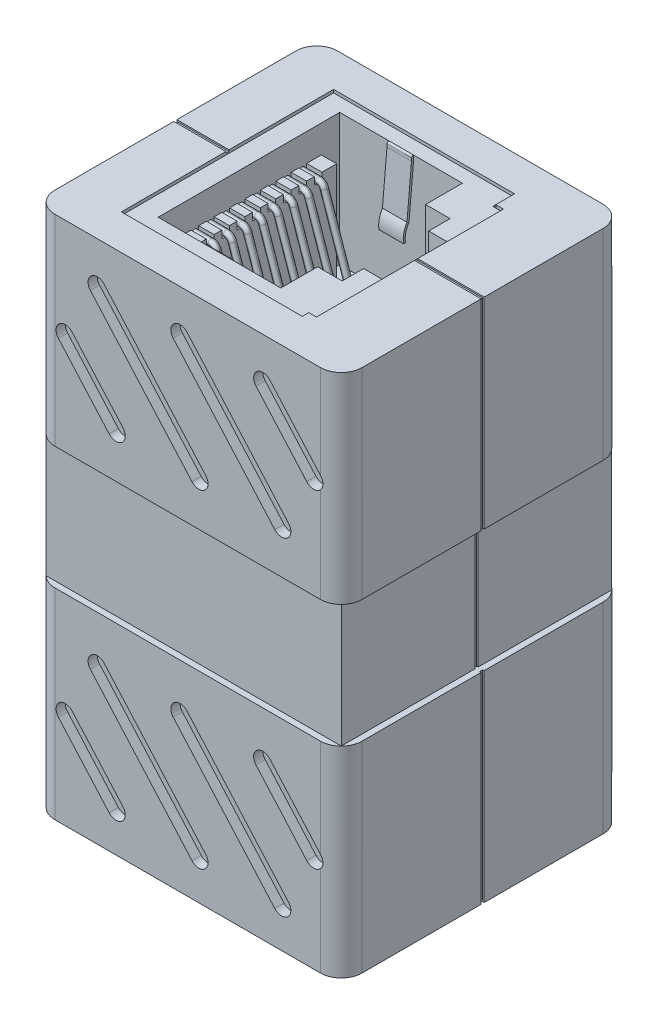
SolidWorks part; units mm, degrees
ref_plane "Front Plane" through (0, 0, 0) normal (0, 0, 1) x (1, 0, 0)
ref_plane "Top Plane" through (0, 0, 0) normal (0, 1, 0) x (1, 0, 0)
ref_plane "Right Plane" through (0, 0, 0) normal (1, 0, 0) x (0, 0, -1)
sketch "Sketch1" plane through (0, 0, 0) normal (0, 1, 0) x (1, 0, 0)
  line L0 (-9.3987, 11.8197) -> (9.9053, 11.8197)
  line L1 (-12.4726, 8.7458) -> (-12.4726, -8.5262)
  line L2 (-9.3987, -11.6) -> (9.9053, -11.6)
  line L3 (12.9792, 8.7458) -> (12.9792, -8.5262)
  line L4 (-12.4726, -8.5262) -> (-12.4726, -11.6)
  line L5 (-12.4726, 8.7458) -> (-12.4726, 11.8197)
  line L6 (-12.4726, -11.6) -> (-9.3987, -11.6)
  line L7 (9.9053, 11.8197) -> (12.9792, 11.8197)
  line L8 (-12.4726, 11.8197) -> (-9.3987, 11.8197)
  line L9 (12.9792, -8.5262) -> (12.9792, -11.6)
  line L10 (12.9792, 11.8197) -> (12.9792, 8.7458)
  line L11 (12.9792, -11.6) -> (9.9053, -11.6)
  dimension "D1" = 19.304
  dimension "D2" = 17.272
extrude "Boss-Extrude1" add sketch "Sketch1" along normal blind 43.434
ref_plane "Plane1" through (0, 43.434, 0) normal (0, 1, 0) x (1, 0, 0)
sketch "Sketch5" plane through (0, 43.434, 0) normal (0, 1, 0) x (1, 0, 0)
  line L0 (12.9792, 11.8197) -> (-12.4726, 11.8197) construction
  line L1 (6.7044, 8.7717) -> (-8.0276, 8.7717)
  line L2 (6.7044, 8.7717) -> (6.7044, 7.2218)
  line L3 (6.7044, -8.552) -> (-8.0276, -8.552)
  line L4 (-8.0276, 8.7717) -> (-8.0276, -8.552)
  line L5 (-12.4726, -11.6) -> (12.9792, -11.6) construction
  line L6 (6.8314, 8.8987) -> (6.8314, 7.3488)
  line L7 (-12.4726, 11.8197) -> (-12.4726, -11.6) construction
  line L8 (-8.1546, 8.8987) -> (-8.1546, -8.679)
  line L9 (6.7044, -8.0182) -> (6.7044, -8.552)
  line L10 (6.7044, -8.0182) -> (7.3394, -8.0182)
  line L11 (-8.1546, -8.679) -> (6.8314, -8.679)
  line L12 (6.7044, 7.2218) -> (7.3394, 7.2218)
  line L13 (7.3394, -8.0182) -> (7.3394, 7.2218)
  line L14 (6.8314, -8.679) -> (6.8314, -8.1452)
  line L15 (6.8314, -8.1452) -> (7.4664, -8.1452)
  line L16 (7.4664, -8.1452) -> (7.4664, 7.3488)
  line L17 (7.4664, 7.3488) -> (6.8314, 7.3488)
  line L19 (6.8314, 8.8987) -> (-8.1546, 8.8987)
  dimension "D1" = 3.048
  dimension "D2" = 3.048
  dimension "D3" = 4.445
  dimension "D4" = 14.732
  dimension "D5" = 0.127
  dimension "D6" = 0.127
  dimension "D7" = 0.127
  dimension "D8" = 0.127
  dimension "D9" = 0.127
  dimension "D10" = 0.127
  dimension "D11" = 0.127
  dimension "D12" = 0.127
extrude "Cut-Extrude4" cut sketch "Sketch5" against normal blind 0.254
sketch "Sketch6" plane through (0, 43.434, 0) normal (0, 1, 0) x (1, 0, 0)
  line L0 (-12.4726, 11.8197) -> (-12.4726, -11.6) construction
  line L1 (12.9792, 0.2368) -> (-12.4726, 0.2368)
  line L2 (12.9792, -0.0172) -> (12.9792, 0.2368)
  line L3 (12.9792, -0.0172) -> (-12.4726, -0.0172)
  line L4 (-12.4726, 0.2368) -> (-12.4726, -0.0172)
  line L5 (-12.4726, 0.1098) -> (-12.4726, -0.0172) construction
  line L6 (-12.4726, 0.1098) -> (-12.4726, 0.2368) construction
  point P0 (-12.4726, 0.1098)
  dimension "D1" = 0.254
  dimension "D2" = 0
extrude "Cut-Extrude7" cut sketch "Sketch6" against normal blind 0.127
sketch "Sketch7" plane through (12.9792, 0, 0) normal (1, 0, 0) x (0, 0, -1)
  line L0 (-0.0172, 43.307) -> (0.2368, 43.307)
  line L1 (0.2368, 43.307) -> (0.2368, 0)
  line L2 (-11.6, 0) -> (11.8197, 0) construction
  line L3 (0.2368, 0) -> (-0.0172, 0)
  line L4 (-0.0172, 0) -> (-0.0172, 43.307)
extrude "Cut-Extrude8" cut sketch "Sketch7" against normal blind 0.127
sketch "Sketch8" plane through (-12.4726, 0, 0) normal (-1, 0, 0) x (0, 0, 1)
  line L0 (-0.2368, 43.307) -> (0.0172, 43.307)
  line L1 (0.0172, 43.307) -> (0.0172, 0)
  line L2 (-0.2368, 0) -> (-0.2368, 43.307)
  line L3 (-0.2368, 0) -> (0.0172, 0)
  line L4 (-11.8197, 0) -> (11.6, 0) construction
extrude "Cut-Extrude9" cut sketch "Sketch8" against normal blind 0.127
sketch "Sketch9" plane through (0, 0, 0) normal (0, -1, 0) x (1, 0, 0)
  line L0 (-12.3456, 0.0172) -> (-12.3456, -0.2368)
  line L1 (-12.3456, -0.2368) -> (12.8522, -0.2368)
  line L2 (12.8522, -0.2368) -> (12.8522, 0.0172)
  line L3 (12.8522, 0.0172) -> (-12.3456, 0.0172)
extrude "Cut-Extrude10" cut sketch "Sketch9" against normal blind 0.127
sketch "Sketch10" plane through (0, 0, 11.6) normal (0, 0, 1) x (1, 0, 0)
  line L0 (0.2533, 43.434) -> (0.2533, 0) construction
  line L3 (-12.4726, 43.434) -> (12.9792, 43.434) construction
  line L4 (-17.0116, 16.637) -> (17.5183, 16.637)
  line L5 (-17.0116, 16.637) -> (-17.0116, 26.797)
  line L6 (-17.0116, 26.797) -> (17.5183, 26.797)
  line L7 (17.5183, 16.637) -> (17.5183, 26.797)
  line L8 (-17.0116, 16.637) -> (17.5183, 26.797) construction
  line L9 (-17.0116, 26.797) -> (17.5183, 16.637) construction
  line L10 (-12.4726, 0) -> (12.9792, 0) construction
  line L11 (0.2533, 21.717) -> (12.9792, 21.717) construction
  line L12 (12.9792, 43.434) -> (12.9792, 0) construction
  point P6 (0.2533, 21.717)
  dimension "D1" = 10.16
  dimension "D2" = 0
extrude "Cut-Extrude11" cut sketch "Sketch10" against normal blind 0.508
sketch "Sketch11" plane through (12.9792, 0, 0) normal (1, 0, 0) x (0, 0, -1)
  line L0 (-0.0172, 21.717) -> (-11.092, 21.717) construction
  line L1 (-0.0172, 0) -> (-0.0172, 43.434) construction
  line L2 (-11.092, 26.797) -> (-11.092, 16.637) construction
  line L4 (-13.4166, 16.637) -> (13.3823, 16.637)
  line L5 (-13.4166, 16.637) -> (-13.4166, 26.797)
  line L6 (-13.4166, 26.797) -> (13.3823, 26.797)
  line L7 (13.3823, 16.637) -> (13.3823, 26.797)
  line L8 (-13.4166, 16.637) -> (13.3823, 26.797) construction
  line L9 (-13.4166, 26.797) -> (13.3823, 16.637) construction
  dimension "D1" = 10.16
extrude "Cut-Extrude12" cut sketch "Sketch11" against normal blind 0.508
sketch "Sketch12" plane through (0, 0, -11.8197) normal (0, 0, -1) x (-1, 0, 0)
  line L0 (-0.2533, 0) -> (-0.2533, 43.7001) construction
  line L1 (-12.9792, 0) -> (12.4726, 0) construction
  line L3 (-14.7409, 16.7701) -> (14.2342, 16.7701)
  line L4 (-14.7409, 16.7701) -> (-14.7409, 26.9301)
  line L5 (-14.7409, 26.9301) -> (14.2342, 26.9301)
  line L6 (14.2342, 16.7701) -> (14.2342, 26.9301)
  line L7 (-14.7409, 16.7701) -> (14.2342, 26.9301) construction
  line L8 (-14.7409, 26.9301) -> (14.2342, 16.7701) construction
  point P4 (-0.2533, 21.8501)
  dimension "D1" = 10.16
extrude "Cut-Extrude13" cut sketch "Sketch12" against normal blind 0.508
sketch "Sketch13" plane through (-12.4726, 0, 0) normal (-1, 0, 0) x (0, 0, 1)
  line L0 (0.0172, 21.717) -> (9.2132, 21.717) construction
  line L1 (0.0172, 0) -> (0.0172, 43.434) construction
  line L3 (-17.8132, 16.637) -> (17.8475, 16.637)
  line L4 (-17.8132, 16.637) -> (-17.8132, 26.797)
  line L5 (-17.8132, 26.797) -> (17.8475, 26.797)
  line L6 (17.8475, 16.637) -> (17.8475, 26.797)
  line L7 (-17.8132, 16.637) -> (17.8475, 26.797) construction
  line L8 (-17.8132, 26.797) -> (17.8475, 16.637) construction
  dimension "D1" = 10.16
extrude "Cut-Extrude14" cut sketch "Sketch13" against normal blind 0.508
sketch "Sketch14" plane through (-11.9646, 0, 0) normal (-1, 0, 0) x (0, 0, 1)
  line L0 (-0.2368, 26.797) -> (0.0172, 26.797)
  line L1 (0.0172, 26.797) -> (0.0172, 16.637)
  line L2 (0.0172, 16.637) -> (-0.2368, 16.637)
  line L3 (-0.2368, 16.637) -> (-0.2368, 26.797)
extrude "Cut-Extrude15" cut sketch "Sketch14" against normal blind 0.127
sketch "Sketch15" plane through (12.4712, 0, 0) normal (1, 0, 0) x (0, 0, -1)
  line L0 (-0.0172, 26.797) -> (0.2368, 26.797)
  line L1 (0.2368, 26.797) -> (0.2368, 16.637)
  line L2 (0.2368, 16.637) -> (-0.0172, 16.637)
  line L3 (-0.0172, 16.637) -> (-0.0172, 26.797)
extrude "Cut-Extrude16" cut sketch "Sketch15" against normal blind 0.127
sketch "Sketch16" plane through (0, 0, -11.8197) normal (0, 0, -1) x (-1, 0, 0)
  line L0 (-6.486, 39.9428) -> (12.1668, 39.9428) construction
  line L1 (7.23, 39.9428) -> (-1.1844, 30.4303) construction
  line L2 (5.6736, 30.4303) -> (-11.4552, 30.4303) construction
  line L3 (7.23, 12.7648) -> (-1.1844, 3.2523) construction
  line L4 (7.8008, 12.2599) -> (-0.6137, 2.7474)
  line L5 (7.8008, 39.4379) -> (-0.6137, 29.9254)
  line L6 (6.6593, 40.4476) -> (-1.7552, 30.9351)
  line L7 (0.372, 39.9428) -> (-8.0424, 30.4303) construction
  line L8 (0.9428, 39.4379) -> (-7.4717, 29.9254)
  line L9 (-0.1987, 40.4476) -> (-8.6132, 30.9351)
  line L10 (9.8808, 35.1865) -> (5.6736, 30.4303) construction
  line L11 (10.4515, 34.6816) -> (6.2443, 29.9254)
  line L12 (9.31, 35.6914) -> (5.1028, 30.9351)
  line L13 (-6.486, 39.9428) -> (-10.6932, 35.1865) construction
  line L14 (-5.9152, 39.4379) -> (-10.1225, 34.6816)
  line L15 (-7.0567, 40.4476) -> (-11.264, 35.6914)
  line L16 (-12.9792, 43.434) -> (-12.9792, 26.9301) construction
  line L17 (6.6593, 13.2696) -> (-1.7552, 3.7571)
  line L18 (0.372, 12.7648) -> (-8.0424, 3.2523) construction
  line L19 (0.9428, 12.2599) -> (-7.4717, 2.7474)
  line L20 (-0.1987, 13.2696) -> (-8.6132, 3.7571)
  line L21 (9.8808, 8.0085) -> (5.6736, 3.2523) construction
  line L22 (10.4515, 7.5036) -> (6.2443, 2.7474)
  line L23 (9.31, 8.5134) -> (5.1028, 3.7571)
  line L24 (-6.486, 12.7648) -> (-10.6932, 8.0085) construction
  line L25 (-5.9152, 12.2599) -> (-10.1225, 7.5036)
  line L26 (-7.0567, 13.2696) -> (-11.264, 8.5134)
  arc A0 (7.8008, 39.4379) -> (6.6593, 40.4476) centre (7.23, 39.9428) ccw
  arc A1 (-1.7552, 30.9351) -> (-0.6137, 29.9254) centre (-1.1844, 30.4303) ccw
  arc A2 (0.9428, 39.4379) -> (-0.1987, 40.4476) centre (0.372, 39.9428) ccw
  arc A3 (-8.6132, 30.9351) -> (-7.4717, 29.9254) centre (-8.0424, 30.4303) ccw
  arc A4 (10.4515, 34.6816) -> (9.31, 35.6914) centre (9.8808, 35.1865) ccw
  arc A5 (5.1028, 30.9351) -> (6.2443, 29.9254) centre (5.6736, 30.4303) ccw
  arc A6 (-5.9152, 39.4379) -> (-7.0567, 40.4476) centre (-6.486, 39.9428) ccw
  arc A7 (-11.264, 35.6914) -> (-10.1225, 34.6816) centre (-10.6932, 35.1865) ccw
  arc A8 (7.8008, 12.2599) -> (6.6593, 13.2696) centre (7.23, 12.7648) ccw
  arc A9 (-1.7552, 3.7571) -> (-0.6137, 2.7474) centre (-1.1844, 3.2523) ccw
  arc A10 (0.9428, 12.2599) -> (-0.1987, 13.2696) centre (0.372, 12.7648) ccw
  arc A11 (-8.6132, 3.7571) -> (-7.4717, 2.7474) centre (-8.0424, 3.2523) ccw
  arc A12 (10.4515, 7.5036) -> (9.31, 8.5134) centre (9.8808, 8.0085) ccw
  arc A13 (5.1028, 3.7571) -> (6.2443, 2.7474) centre (5.6736, 3.2523) ccw
  arc A14 (-5.9152, 12.2599) -> (-7.0567, 13.2696) centre (-6.486, 12.7648) ccw
  arc A15 (-11.264, 8.5134) -> (-10.1225, 7.5036) centre (-10.6932, 8.0085) ccw
  point P10 (3.0228, 35.1865)
  point P15 (-3.8352, 35.1865)
  point P22 (7.7772, 32.8084)
  point P29 (-8.5896, 37.5646)
  point P36 (-12.9792, 35.182)
  point P39 (3.0228, 8.0085)
  point P44 (-3.8352, 8.0085)
  point P51 (7.7772, 5.6304)
  point P58 (-8.5896, 10.3866)
  dimension "D2" = 12.7
  dimension "D3" = 6.35
  dimension "D4" = 6.35
  dimension "D5" = 1.524
  dimension "D6" = 1.524
  dimension "D7" = 1.524
  dimension "D8" = 1.524
  dimension "D9" = 6.858
  dimension "D10" = 6.858
  dimension "D11" = 6.858
  dimension "D12" = 2.286
  dimension "D13" = 12.7
extrude "Cut-Extrude17" cut sketch "Sketch16" against normal blind 0.762
ref_plane "Plane4" through (0, 0, -0.1098) normal (0, 0, -1) x (-1, 0, 0)
mirror "Mirror1" about plane through (0, 0, -0.1098) normal (0, 0, -1) of "Cut-Extrude17"
sketch "Sketch17" plane through (0, 43.434, 0) normal (0, 1, 0) x (1, 0, 0)
  line L0 (6.7044, -8.0182) -> (6.7044, -8.552)
  line L1 (-8.0276, 8.7717) -> (6.7044, 8.7717)
  line L2 (-8.0276, 8.7717) -> (-8.0276, -8.552)
  line L3 (-8.0276, -8.552) -> (6.7044, -8.552)
  line L4 (6.7044, 8.7717) -> (6.7044, 7.2218)
  line L5 (7.3394, -8.0182) -> (6.7044, -8.0182)
  line L6 (7.3394, -8.0182) -> (7.3394, 7.2218)
  line L7 (7.3394, 7.2218) -> (6.7044, 7.2218)
extrude "Cut-Extrude18" cut sketch "Sketch17" against normal blind 0.127
sketch "Sketch18" plane through (0, 43.307, 0) normal (0, 1, 0) x (1, 0, 0)
  line L0 (3.7834, -4.3621) -> (3.7834, -7.4101)
  line L1 (-6.3766, 7.6297) -> (3.7834, 7.6297)
  line L2 (-6.3766, 7.6297) -> (-6.3766, -7.4101)
  line L3 (-6.3766, -7.4101) -> (3.7834, -7.4101)
  line L4 (3.7834, 7.6297) -> (3.7834, 4.5817)
  line L5 (3.7834, 4.5817) -> (5.8154, 4.5817)
  line L6 (5.8154, -2.5841) -> (5.8154, -4.3621)
  line L7 (3.7834, -4.3621) -> (5.8154, -4.3621)
  line L8 (5.8154, 4.5817) -> (5.8154, 2.8037)
  line L9 (5.8154, 2.8037) -> (7.3394, 2.8037)
  line L11 (5.8154, -2.5841) -> (7.3394, -2.5841)
  line L12 (7.4664, 0.2368) -> (7.4664, 7.3488) construction
  line L13 (-6.3766, 0.1098) -> (-5.755, 0.1098) construction
  line L16 (-8.0276, 0.1098) -> (-7.4203, 0.1098) construction
  line L17 (-8.0276, 8.7717) -> (-8.0276, -8.552) construction
  line L18 (7.3394, 2.8037) -> (7.4664, 2.8037)
  line L19 (7.4664, 2.8037) -> (7.4664, -2.5841)
  line L20 (7.4664, -2.5841) -> (7.3394, -2.5841)
  dimension "D1" = 3.048
  dimension "D2" = 3.048
  dimension "D3" = 1.778
  dimension "D4" = 1.778
  dimension "D5" = 2.032
  dimension "D6" = 1.524
  dimension "D7" = 0
  dimension "D8" = 10.16
extrude "Cut-Extrude19" cut sketch "Sketch18" against normal blind 0.762
sketch "Sketch20" plane through (0, 42.545, 0) normal (0, 1, 0) x (1, 0, 0)
  line L0 (-6.3766, -7.4101) -> (3.7834, -7.4101)
  line L1 (3.7834, -7.4101) -> (3.7834, -4.3621)
  line L2 (3.7834, -4.3621) -> (5.8154, -4.3621)
  line L3 (5.8154, -4.3621) -> (5.8154, -2.5841)
  line L4 (5.8154, -2.5841) -> (6.5774, -2.5841)
  line L6 (6.5774, -2.5841) -> (6.5774, 2.8037)
  line L7 (7.3394, 2.8037) -> (5.8154, 2.8037) construction
  line L8 (6.5774, 2.8037) -> (5.8154, 2.8037)
  line L9 (5.8154, 2.8037) -> (5.8154, 4.5817)
  line L10 (5.8154, 4.5817) -> (3.7834, 4.5817)
  line L11 (3.7834, 4.5817) -> (3.7834, 7.6297)
  line L12 (3.7834, 7.6297) -> (-6.3766, 7.6297)
  line L13 (-6.3766, 7.6297) -> (-6.3766, -7.4101)
extrude "Cut-Extrude20" cut sketch "Sketch20" against normal blind 10.16
fillet "Fillet1" radius 1.7272 16 edges at (12.9792, 8.3185, 11.6) (-12.4726, 8.3185, 11.6) (-12.4726, 35.1155, 11.6) (-12.4726, 35.182, -11.8197) (12.9792, 35.182, -11.8197) (12.9792, 35.1155, 11.6) (12.9792, 8.3185, -11.8197) (12.7252, 16.637, -11.8197) (12.4712, 16.7035, -11.8197) (-12.4726, 26.9301, -11.5657) (12.9792, 26.9301, -11.5657) (-12.4726, 26.8635, -11.3117) (12.9792, 26.8635, -11.3117) (-12.4726, 8.3185, -11.8197) (-12.2186, 16.637, -11.8197) (-11.9646, 16.7035, -11.8197)
ref_plane "Plane5" through (-1.2966, 0, 0) normal (-1, 0, 0) x (0, 0, 1)
sketch "Sketch21" plane through (-1.2966, 0, 0) normal (-1, 0, 0) x (0, 0, 1)
  line L0 (-7.4785, 42.9304) -> (-7.1025, 38.7375)
  line L1 (-8.8987, 43.18) -> (8.679, 43.18) construction
  line L2 (-7.6297, 32.385) -> (-7.6297, 43.307) construction
  line L3 (-7.2722, 38.6632) -> (-7.6297, 42.6506)
  line L4 (-6.8187, 37.3348) -> (-6.9856, 37.3348)
  line L6 (-0.1098, 32.385) -> (-0.1098, 44.847) construction
  line L7 (-7.6297, 32.385) -> (7.4101, 32.385) construction
  line L8 (-7.6297, 43.18) -> (-7.6297, 42.6506)
  line L10 (7.4101, 43.307) -> (7.4101, 43.18)
  line L11 (7.2734, 43.1621) -> (7.2589, 42.9304)
  line L12 (7.4101, 43.18) -> (7.4101, 42.6506)
  line L13 (-7.4931, 43.1621) -> (-7.4785, 42.9304)
  line L15 (-7.6297, 43.307) -> (-7.6297, 43.18)
  line L17 (6.599, 37.3348) -> (6.766, 37.3348)
  line L18 (7.0525, 38.6632) -> (7.4101, 42.6506)
  line L19 (7.2589, 42.9304) -> (6.8829, 38.7375)
  spline S0 degree 2 poles (-7.1025, 38.7375) (-6.7036, 38.0831) (-6.8187, 37.3348) knots 0 0 0 1 1 1
  spline S1 degree 2 poles (-6.9856, 37.3348) (-6.8588, 38.0538) (-7.2722, 38.6632) knots 0 0 0 1 1 1
  spline S2 degree 2 poles (7.4101, 43.307) (7.2928, 43.2827) (7.2734, 43.1621) knots 0 0 0 1 1 1
  spline S3 degree 2 poles (6.766, 37.3348) (6.6391, 38.0538) (7.0525, 38.6632) knots 0 0 0 1 1 1
  spline S4 degree 2 poles (6.8829, 38.7375) (6.4839, 38.0831) (6.599, 37.3348) knots 0 0 0 1 1 1
  spline S6 degree 2 poles (-7.6297, 43.307) (-7.5125, 43.2827) (-7.4931, 43.1621) knots 0 0 0 1 1 1
extrude "Boss-Extrude2" add sketch "Sketch21" along normal blind 1.016 and the other way blind 1.016
sketch "Sketch22" plane through (-6.3766, 0, 0) normal (1, 0, 0) x (0, 0, -1)
  line L0 (6.1057, 32.385) -> (-5.8861, 32.385)
  line L1 (7.6297, 32.385) -> (-7.4101, 32.385) construction
  line L2 (-5.8861, 32.385) -> (-5.8861, 41.021)
  line L3 (-5.8861, 41.021) -> (6.1057, 41.021)
  line L4 (6.1057, 41.021) -> (6.1057, 32.385)
  line L5 (7.6297, 43.307) -> (-7.4101, 43.307) construction
  line L6 (-7.4101, 32.385) -> (-7.4101, 43.307) construction
  line L7 (7.6297, 32.385) -> (7.6297, 43.307) construction
  dimension "D1" = 2.286
  dimension "D2" = 1.524
  dimension "D3" = 1.524
extrude "Boss-Extrude3" add sketch "Sketch22" along normal blind 1.27
sketch "Sketch23" plane through (-5.1066, 0, 0) normal (1, 0, 0) x (0, 0, -1)
  line L0 (6.1057, 41.021) -> (-5.8861, 41.021) construction
  line L1 (6.1057, 32.385) -> (6.1057, 41.021) construction
  line L2 (4.8865, 41.021) -> (4.2515, 41.021)
  line L3 (4.8865, 41.021) -> (4.8865, 40.386)
  line L4 (4.8865, 40.386) -> (4.2515, 40.386)
  line L5 (4.2515, 41.021) -> (4.2515, 40.386)
  line L6 (3.6093, 41.021) -> (2.9743, 41.021)
  line L7 (3.6093, 41.021) -> (3.6093, 40.386)
  line L8 (3.6093, 40.386) -> (2.9743, 40.386)
  line L9 (2.9743, 41.021) -> (2.9743, 40.386)
  line L10 (2.332, 41.021) -> (1.697, 41.021)
  line L11 (2.332, 41.021) -> (2.332, 40.386)
  line L12 (2.332, 40.386) -> (1.697, 40.386)
  line L13 (1.697, 41.021) -> (1.697, 40.386)
  line L14 (1.0548, 41.021) -> (0.4198, 41.021)
  line L15 (1.0548, 41.021) -> (1.0548, 40.386)
  line L16 (1.0548, 40.386) -> (0.4198, 40.386)
  line L17 (0.4198, 41.021) -> (0.4198, 40.386)
  line L18 (-0.2225, 41.021) -> (-0.8575, 41.021)
  line L19 (-0.2225, 41.021) -> (-0.2225, 40.386)
  line L20 (-0.2225, 40.386) -> (-0.8575, 40.386)
  line L21 (-0.8575, 41.021) -> (-0.8575, 40.386)
  line L22 (-1.4998, 41.021) -> (-2.1348, 41.021)
  line L23 (-1.4998, 41.021) -> (-1.4998, 40.386)
  line L24 (-1.4998, 40.386) -> (-2.1348, 40.386)
  line L25 (-2.1348, 41.021) -> (-2.1348, 40.386)
  line L26 (-2.777, 41.021) -> (-3.412, 41.021)
  line L27 (-2.777, 41.021) -> (-2.777, 40.386)
  line L28 (-2.777, 40.386) -> (-3.412, 40.386)
  line L29 (-3.412, 41.021) -> (-3.412, 40.386)
  line L30 (-4.0543, 41.021) -> (-4.6893, 41.021)
  line L31 (-4.0543, 41.021) -> (-4.0543, 40.386)
  line L32 (-4.0543, 40.386) -> (-4.6893, 40.386)
  line L33 (-4.6893, 41.021) -> (-4.6893, 40.386)
  dimension "D1" = 0.635
  dimension "D2" = 0.635
  dimension "D3" = 1.2192
  dimension "D4" = 8
extrude "Cut-Extrude24" cut sketch "Sketch23" against normal blind 1.27
sketch "Sketch25" plane through (0, 32.385, 0) normal (0, 1, 0) x (1, 0, 0)
  line L0 (-2.3163, 3.6165) -> (-2.3163, 2.9815)
  line L1 (-1.6813, 4.8865) -> (-2.3163, 4.8865)
  line L2 (-1.6813, 4.8865) -> (-1.6813, 4.2515)
  line L3 (-1.6813, 4.2515) -> (-2.3163, 4.2515)
  line L4 (-2.3163, 4.8865) -> (-2.3163, 4.2515)
  line L5 (-1.6813, 2.9815) -> (-2.3163, 2.9815)
  line L6 (-1.6813, 3.6165) -> (-1.6813, 2.9815)
  line L7 (-1.6813, 3.6165) -> (-2.3163, 3.6165)
  line L8 (-2.3163, 2.3465) -> (-2.3163, 1.7115)
  line L9 (-1.6813, 1.7115) -> (-2.3163, 1.7115)
  line L10 (-1.6813, 2.3465) -> (-1.6813, 1.7115)
  line L11 (-1.6813, 2.3465) -> (-2.3163, 2.3465)
  line L12 (-2.3163, 1.0765) -> (-2.3163, 0.4415)
  line L13 (-1.6813, 0.4415) -> (-2.3163, 0.4415)
  line L14 (-1.6813, 1.0765) -> (-1.6813, 0.4415)
  line L15 (-1.6813, 1.0765) -> (-2.3163, 1.0765)
  line L16 (-2.3163, -0.1935) -> (-2.3163, -0.8285)
  line L17 (-1.6813, -0.8285) -> (-2.3163, -0.8285)
  line L18 (-1.6813, -0.1935) -> (-1.6813, -0.8285)
  line L19 (-1.6813, -0.1935) -> (-2.3163, -0.1935)
  line L20 (-2.3163, -1.4635) -> (-2.3163, -2.0985)
  line L21 (-1.6813, -2.0985) -> (-2.3163, -2.0985)
  line L22 (-1.6813, -1.4635) -> (-1.6813, -2.0985)
  line L23 (-1.6813, -1.4635) -> (-2.3163, -1.4635)
  line L24 (-2.3163, -2.7335) -> (-2.3163, -3.3685)
  line L25 (-1.6813, -3.3685) -> (-2.3163, -3.3685)
  line L26 (-1.6813, -2.7335) -> (-1.6813, -3.3685)
  line L27 (-1.6813, -2.7335) -> (-2.3163, -2.7335)
  line L28 (-2.3163, -4.0035) -> (-2.3163, -4.6385)
  line L29 (-1.6813, -4.6385) -> (-2.3163, -4.6385)
  line L30 (-1.6813, -4.0035) -> (-1.6813, -4.6385)
  line L31 (-1.6813, -4.0035) -> (-2.3163, -4.0035)
  dimension "D1" = 0.635
  dimension "D2" = 0.635
  dimension "D3" = 1.2192
extrude "Cut-Extrude25" cut sketch "Sketch25" against normal blind 1.27
sketch "Sketch26" plane through (0, 0, -4.2515) normal (0, 0, -1) x (-1, 0, 0)
  line L0 (4.2948, 40.4431) -> (1.9515, 33.6217)
  line L1 (6.3766, 32.385) -> (6.3766, 43.307) construction
  line L2 (2.4595, 33.5368) -> (4.7753, 40.278)
  line L3 (6.3766, 40.9575) -> (5.0155, 40.9575)
  line L4 (6.3766, 40.9575) -> (6.3766, 40.4495)
  line L5 (6.3766, 40.4495) -> (5.0155, 40.4495)
  line L6 (6.3766, 40.7035) -> (6.0778, 40.7035) construction
  line L7 (2.3163, 31.115) -> (1.6813, 31.115) construction
  line L8 (1.7448, 31.115) -> (2.2528, 31.115)
  line L9 (1.7448, 32.3838) -> (1.7448, 31.115)
  line L11 (2.2528, 31.115) -> (2.2528, 32.0879)
  line L12 (5.1066, 41.021) -> (5.1066, 40.386) construction
  line L14 (2.2528, 32.0879) -> (2.2528, 32.299)
  line L16 (5.1066, 40.7035) -> (5.3961, 40.7035) construction
  line L18 (1.9988, 31.115) -> (1.9988, 31.3912) construction
  line L19 (2.3163, 32.385) -> (1.6813, 32.385) construction
  line L20 (1.9988, 32.385) -> (1.9988, 32.2057) construction
  arc A0 (1.7448, 32.3838) -> (1.9515, 33.6217) centre (5.5548, 32.3838) cw
  arc A1 (2.4595, 33.5368) -> (2.2528, 32.299) centre (6.0628, 32.299) ccw
  arc A2 (4.7753, 40.278) -> (5.0155, 40.4495) centre (5.0155, 40.1955) cw
  arc A3 (4.2948, 40.4431) -> (5.0155, 40.9575) centre (5.0155, 40.1955) cw
  dimension "D9" = 0.254
  dimension "D10" = 0.762
  dimension "D4" = 3.81
  dimension "D2" = 0.508
  dimension "D3" = 0.508
extrude "Boss-Extrude4" add sketch "Sketch26" along normal blind 0.508 separate body
fillet "Fillet2" radius 0.254 20 edges at (-2.2528, 31.707, -4.7595) (-2.3048, 32.9265, -4.7595) (-5.696, 40.4495, -4.7595) (-4.8679, 40.4022, -4.7595) (-5.696, 40.9575, -4.7595) (-4.5728, 40.8157, -4.7595) (-1.7448, 31.7494, -4.7595) (-1.7968, 33.0113, -4.7595) (-2.2528, 31.707, -4.2515) (-2.3048, 32.9265, -4.2515) (-5.696, 40.4495, -4.2515) (-4.8679, 40.4022, -4.2515) (-5.696, 40.9575, -4.2515) (-4.5728, 40.8157, -4.2515) (-1.7448, 31.7494, -4.2515) (-1.7968, 33.0113, -4.2515) (-3.6174, 36.9074, -4.7595) (-3.1231, 37.0324, -4.7595) (-3.6174, 36.9074, -4.2515) (-3.1231, 37.0324, -4.2515)
pattern_linear "LPattern1" count 8 spacing 1.27 along (0, 0, 1) of bodies 125
ref_plane "Plane8" through (0, 21.717, 0) normal (0, 1, 0) x (1, 0, 0)
mirror "Mirror11" about plane through (0, 21.717, 0) normal (0, 1, 0) of "Cut-Extrude4"
mirror "Mirror12" about plane through (0, 21.717, 0) normal (0, 1, 0) of "Cut-Extrude18"
mirror "Mirror14" about plane through (0, 21.717, 0) normal (0, 1, 0) of "Cut-Extrude19"
mirror "Mirror16" about plane through (0, 21.717, 0) normal (0, 1, 0) of "Cut-Extrude20"
mirror "Mirror17" about plane through (0, 21.717, 0) normal (0, 1, 0) of "Boss-Extrude2"
mirror "Mirror18" about plane through (0, 21.717, 0) normal (0, 1, 0) of "Boss-Extrude3"
mirror "Mirror19" about plane through (0, 21.717, 0) normal (0, 1, 0) of "Cut-Extrude24"
mirror "Mirror20" about plane through (0, 21.717, 0) normal (0, 1, 0) of "Cut-Extrude25"
sketch "Sketch30" plane through (0, 0, 4.0543) normal (0, 0, 1) x (1, 0, 0)
  line L0 (-4.2948, 2.9909) -> (-1.9515, 9.8123)
  line L2 (-2.4595, 9.8972) -> (-4.7753, 3.156)
  line L3 (-6.3766, 2.4765) -> (-5.0155, 2.4765)
  line L4 (-6.3766, 2.4765) -> (-6.3766, 2.9845)
  line L5 (-6.3766, 2.9845) -> (-5.0155, 2.9845)
  line L6 (-6.3766, 2.7305) -> (-6.0778, 2.7305) construction
  line L8 (-1.7448, 12.319) -> (-2.2528, 12.319)
  line L9 (-1.7448, 11.0502) -> (-1.7448, 12.319)
  line L10 (-6.3766, 11.049) -> (-6.3766, 0.127) construction
  line L11 (-2.2528, 12.319) -> (-2.2528, 11.3461)
  line L12 (-5.1066, 2.413) -> (-5.1066, 3.048) construction
  line L13 (-2.3163, 12.319) -> (-1.6813, 12.319) construction
  line L14 (-2.2528, 11.3461) -> (-2.2528, 11.135)
  line L16 (-5.1066, 2.7305) -> (-5.3961, 2.7305) construction
  line L18 (-1.9988, 12.319) -> (-1.9988, 12.0428) construction
  line L19 (-2.3163, 11.049) -> (-1.6813, 11.049) construction
  line L20 (-1.9988, 11.049) -> (-1.9988, 11.2283) construction
  arc A0 (-1.7448, 11.0502) -> (-1.9515, 9.8123) centre (-5.5548, 11.0502) cw
  arc A1 (-2.4595, 9.8972) -> (-2.2528, 11.135) centre (-6.0628, 11.135) ccw
  arc A2 (-4.7753, 3.156) -> (-5.0155, 2.9845) centre (-5.0155, 3.2385) cw
  arc A3 (-4.2948, 2.9909) -> (-5.0155, 2.4765) centre (-5.0155, 3.2385) cw
  dimension "D9" = 0.254
  dimension "D10" = 0.762
  dimension "D4" = 3.81
  dimension "D2" = 0.508
  dimension "D3" = 0.508
extrude "Boss-Extrude5" add sketch "Sketch30" along normal blind 0.508 separate body
fillet "Fillet3" radius 0.254 20 edges at (-2.2528, 11.727, 4.5623) (-2.3048, 10.5075, 4.5623) (-5.696, 2.9845, 4.5623) (-4.8679, 3.0318, 4.5623) (-2.2528, 11.727, 4.0543) (-2.3048, 10.5075, 4.0543) (-5.696, 2.9845, 4.0543) (-4.8679, 3.0318, 4.0543) (-5.696, 2.4765, 4.0543) (-4.5728, 2.6183, 4.0543) (-1.7448, 11.6846, 4.0543) (-1.7968, 10.4227, 4.0543) (-5.696, 2.4765, 4.5623) (-4.5728, 2.6183, 4.5623) (-1.7448, 11.6846, 4.5623) (-1.7968, 10.4227, 4.5623) (-3.6174, 6.5266, 4.5623) (-3.6174, 6.5266, 4.0543) (-3.1231, 6.4016, 4.0543) (-3.1231, 6.4016, 4.5623)
pattern_linear "LPattern7" count 8 spacing 1.27 along (0, 0, -1) of bodies 147
